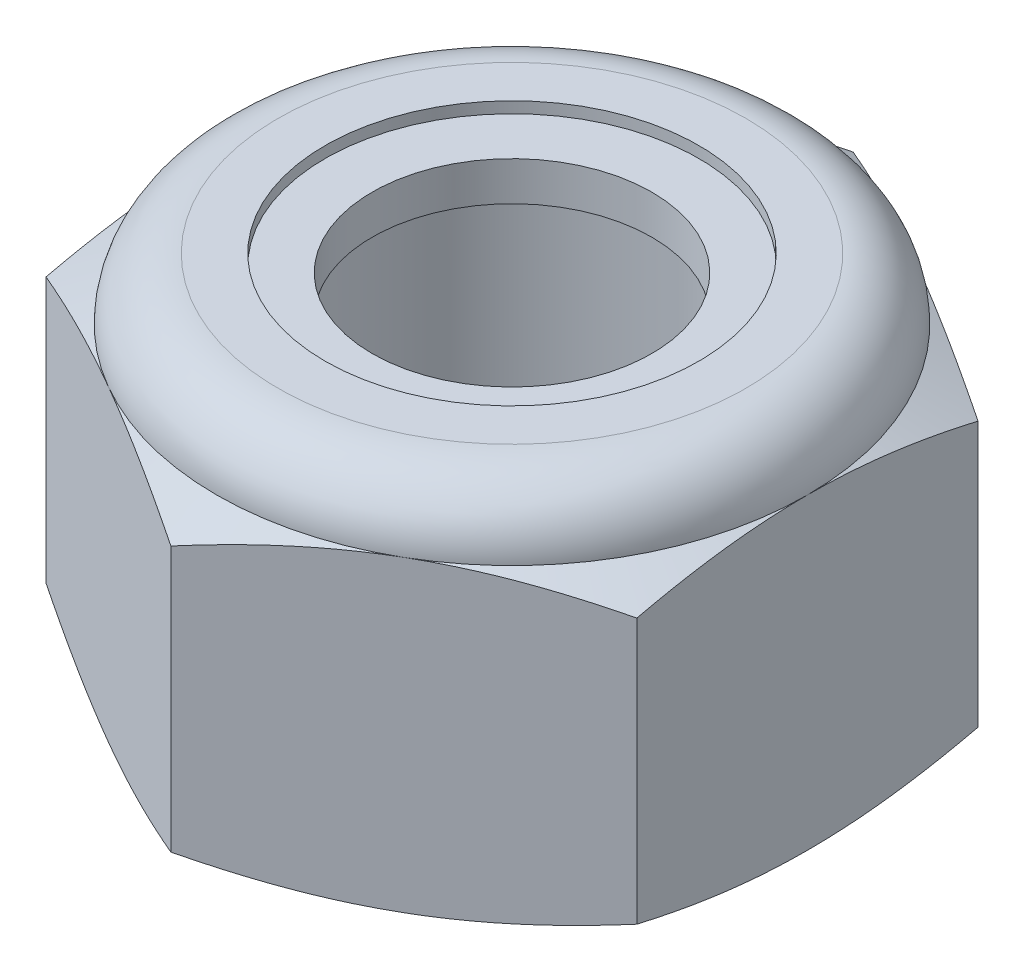
SolidWorks part; units mm, degrees
ref_plane "Front" through (0, 0, 0) normal (0, 0, 1) x (1, 0, 0)
ref_plane "Top" through (0, 0, 0) normal (0, 1, 0) x (1, 0, 0)
ref_plane "Right" through (0, 0, 0) normal (1, 0, 0) x (0, 0, -1)
sketch "Sketch1" plane through (0, 0, 0) normal (0, 1, 0) x (1, 0, 0)
  line L1 (0, 4.6188) -> (-4, 2.3094)
  line L2 (-4, 2.3094) -> (-4, -2.3094)
  line L3 (-4, -2.3094) -> (0, -4.6188)
  line L4 (0, -4.6188) -> (4, -2.3094)
  line L5 (4, -2.3094) -> (4, 2.3094)
  line L6 (4, 2.3094) -> (0, 4.6188)
  circle A0 centre (0, 0) radius 4 construction
  dimension "Hex Flats" = 8
extrude "Extrude1" add sketch "Sketch1" along normal blind 5
sketch "Sketch2" plane through (0, 0, 0) normal (1, 0, 0) x (0, 0, -1)
  line L0 (-2.5, 0) -> (-2.5, 5) construction
  line L1 (0, 0) -> (2.5, 0)
  line L2 (0, 0) -> (0, 5)
  line L3 (0, 5) -> (2.5, 5)
  line L4 (2.5, 0) -> (2.5, 5)
  line L5 (-2.3094, 5) -> (2.3094, 5) construction
  line L7 (0, -2.5) -> (0, 0) construction
  dimension "Thread Dia" = 5
revolve "Revolve1" add sketch "Sketch2" angle 360 about L7
sketch "Sketch8" plane through (0, 0, 0) normal (0, -1, 0) x (1, 0, 0)
  circle A1 centre (0, 0) radius 2.5
  circle A2 centre (0, 0) radius 2.5
  dimension "D1" = 0
curve "Helix/Spiral1" pitch 0.8 height 5.8 turns 7.25 parameters "Pitch"=0.8
sketch "Sketch10" plane through (0, 0, 0) normal (0, -1, 0) x (1, 0, 0)
  circle A1 centre (0, 0) radius 2.5
  circle A2 centre (0, 0) radius 2.5
  dimension "D1" = 0
extrude "Boss-Extrude1" add sketch "Sketch10" against normal through all draft 45
sketch "Sketch11" plane through (0, 5, 0) normal (0, 1, 0) x (1, 0, 0)
  circle A1 centre (0, 0) radius 2.5
  circle A2 centre (0, 0) radius 2.5
  dimension "D1" = 0
extrude "Boss-Extrude2" add sketch "Sketch11" against normal through all draft 45
sketch "Sketch9" [suppressed] plane through (0, 0, 0) normal (1, 0, 0) x (0, 0, -1)
  line L0 (2.5, -0.7) -> (2.5, 0)
  line L1 (2.5, -0.7) -> (1.9804, -0.4)
  line L2 (1.9804, -0.4) -> (1.9804, -0.3)
  line L3 (1.9804, -0.3) -> (2.5, 0)
  line L4 (-2.5, 0) -> (2.5, 0) construction
  line L5 (2.5, -0.35) -> (1.9804, -0.35) construction
  line L6 (2.2402, -0.55) -> (2.2402, -0.15) construction
  dimension "D1" = 0.1
  dimension "D2" = 0.4
  dimension "D3" = 60
sweep "Cut-Sweep1" [suppressed] cut profiles "Sketch9" path "Helix/Spiral1"
combine bodies "Combine1" operation type subtract main body 108 bodies to subtract 134
sketch "Sketch5" plane through (0, 0, 0) normal (1, 0, 0) x (0, 0, -1)
  line L0 (0, 0) -> (4, 0)
  line L1 (4, 0) -> (4.6188, 0.2886)
  line L2 (4.6188, 0.2886) -> (4.6188, 3.8781)
  line L3 (4.6188, 3.8781) -> (4, 4.1667)
  line L4 (3.1667, 5) -> (3.1667, 6.27)
  line L5 (3.1667, 6.27) -> (5.8888, 6.27)
  line L6 (5.8888, 6.27) -> (5.8888, -1.27)
  line L7 (5.8888, -1.27) -> (0, -1.27)
  line L8 (0, -1.27) -> (0, 0)
  line L9 (4, 4.1667) -> (4, 0) construction
  line L10 (0, 0) -> (2.5, 0) construction
  line L13 (4.6188, 2.0833) -> (5.8888, 2.0833) construction
  line L14 (4.6188, 5) -> (4.6188, 0) construction
  line L15 (0, 0) -> (0, 6.27) construction
  line L20 (0, 6.27) -> (3.1667, 6.27) construction
  line L22 (0, 5) -> (2.5, 5) construction
  arc A0 (4, 4.1667) -> (3.1667, 5) centre (3.1667, 4.1667) ccw
  dimension "D1" = 25
  dimension "D2" = 1.27
  dimension "D3" = 5
  dimension "D4" = 0.8333
revolve "Cut-Revolve3" cut sketch "Sketch5" angle 360 about L15
sketch "Sketch6" plane through (0, 0, 0) normal (1, 0, 0) x (0, 0, -1)
  line L0 (0, 4.1667) -> (3.8476, 4.1667)
  line L1 (3.1667, 4.8476) -> (2.5302, 4.8476)
  line L2 (0, 6.27) -> (0, 4.1667)
  line L3 (2.5302, 6.27) -> (0, 6.27)
  line L4 (0, 6.27) -> (3.1667, 6.27) construction
  line L5 (0, 0) -> (0, 6.27) construction
  line L6 (0, 6.27) -> (0, 0) construction
  line L7 (2.5302, 4.8476) -> (2.5302, 6.27)
  line L8 (3.1667, 5) -> (3.1667, 4.8476) construction
  line L9 (2.5302, 4.8476) -> (1.8938, 4.8476) construction
  line L10 (1.8938, 4.8476) -> (1.8938, 0) construction
  line L13 (1.8938, 4.55) -> (2.5, 4.2) construction
  line L15 (2.5, 0) -> (2.5, 5) construction
  line L16 (1.8938, 4.65) -> (2.5, 5) construction
  line L19 (2.1969, 4.375) -> (2.1969, 4.825) construction
  line L20 (1.8938, 4.55) -> (1.8938, 4.65) construction
  line L21 (2.5, 4.2) -> (2.5, 5) construction
  line L22 (2.5, 4.6) -> (1.8938, 4.6) construction
  arc A0 (3.8476, 4.1667) -> (3.1667, 4.8476) centre (3.1667, 4.1667) ccw
  arc A1 (4, 4.1667) -> (3.1667, 5) centre (3.1667, 4.1667) ccw construction
  dimension "D1" = 0.1524
  dimension "D2" = 0.8
  dimension "D3" = 0.1
  dimension "D4" = 60
revolve "Cut-Revolve4" cut sketch "Sketch6" angle 360 about L6
sketch "Sketch7" plane through (0, 0, 0) normal (1, 0, 0) x (0, 0, -1)
  line L0 (1.8938, 4.2429) -> (3.7666, 4.2429)
  line L1 (3.1667, 4.7714) -> (1.8938, 4.7714)
  line L2 (1.8938, 4.7714) -> (1.8938, 4.2429)
  line L3 (1.8938, 4.2429) -> (0, 4.2429) construction
  line L4 (0, 4.2429) -> (0, 4.7714) construction
  line L5 (0, 4.7714) -> (1.8938, 4.7714) construction
  line L6 (1.8938, 4.2429) -> (1.8938, 4.1667) construction
  line L7 (0, 4.1667) -> (3.8476, 4.1667) construction
  line L8 (3.1667, 4.7714) -> (3.1667, 4.8476) construction
  line L9 (1.8938, 4.8476) -> (1.8938, 0) construction
  arc A0 (3.7666, 4.2429) -> (3.1667, 4.7714) centre (3.1667, 4.1667) ccw
  arc A2 (3.8476, 4.1667) -> (3.1667, 4.8476) centre (3.1667, 4.1667) ccw construction
  dimension "D1" = 0.0762
revolve "Revolve2" add sketch "Sketch7" angle 360 about L4
equation "\"D4@Sketch5\"=\"Height@Extrude1\"/6"
equation "\"D3@Helix/Spiral1\"=\"Pitch@Helix/Spiral1\"+\"Height@Extrude1\""
equation "\"D1@Sketch9\"=\"Pitch@Helix/Spiral1\"*.125"
equation "\"D2@Sketch9\"=\"Pitch@Helix/Spiral1\"*.50"
equation "\"D2@Sketch6\"=\"Pitch@Helix/Spiral1\""
equation "\"D3@Sketch6\"=\"Pitch@Helix/Spiral1\"/8"
